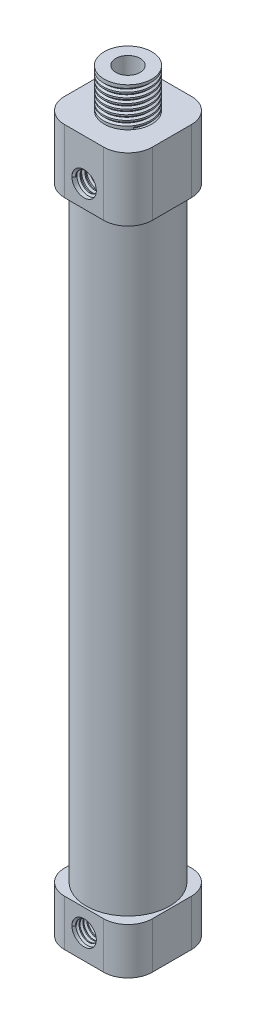
SolidWorks part; units mm, degrees
ref_plane "前视基准面" through (0, 0, 0) normal (0, 0, 1) x (1, 0, 0)
ref_plane "上视基准面" through (0, 0, 0) normal (0, 1, 0) x (1, 0, 0)
ref_plane "右视基准面" through (0, 0, 0) normal (1, 0, 0) x (0, 0, -1)
sketch "草图1" plane through (0, 0, 0) normal (0, 1, 0) x (1, 0, 0)
  circle A0 centre (0, 0) radius 8.54
  dimension "D1" = 17.08
extrude "凸台-拉伸1" add sketch "草图1" along normal blind 124
sketch "草图2" plane through (0, 124, 0) normal (0, 1, 0) x (1, 0, 0)
  line L1 (-9, -9) -> (9, -9)
  line L2 (-9, -9) -> (-9, 9)
  line L3 (-9, 9) -> (9, 9)
  line L4 (9, -9) -> (9, 9)
  line L5 (-9, -9) -> (9, 9) construction
  line L6 (-9, 9) -> (9, -9) construction
  point P0 (0, 0)
  dimension "D1" = 18
extrude "凸台-拉伸2" add sketch "草图2" along normal blind 13
fillet "圆角1" radius 5 4 edges at (9, 130.5, -9) (-9, 130.5, -9) (-9, 130.5, 9) (9, 130.5, 9)
sketch "草图3" plane through (0, 0, 9) normal (0, 0, 1) x (1, 0, 0)
  line L0 (0, 138.947) -> (0, 120.0596) construction
  line L1 (-4, 137) -> (4, 137) construction
  circle A0 centre (0, 128.5) radius 2.5
  dimension "D1" = 5
  dimension "D2" = 6
sketch "草图4" plane through (0, 137, 0) normal (0, 1, 0) x (1, 0, 0)
  circle A0 centre (0, 0) radius 4.875
  dimension "D1" = 9.75
extrude "凸台-拉伸3" add sketch "草图4" along normal blind 8
thread "螺纹线1" pitch 0.7937 method cut profile "螺纹线轮廓1" start angle 0, offset 0, length 7.6, pitch 1, diameter 9.75
ref_plane "基准面1" through (-4.875, 145, 0) normal (0, 0, 1) x (-1, 0, 0)
sketch "螺纹线轮廓1" plane through (-4.875, 145, 0) normal (0, 0, 1) x (-1, 0, 0)
  line L0 (0, 0) -> (0, 0.7937) construction
  line L11 (0, 0) -> (0, 0.6945)
  line L12 (0, 0.6945) -> (-0.4296, 0.4465)
  line L13 (-0.4296, 0.4465) -> (-0.4296, 0.248)
  line L15 (-0.4296, 0.248) -> (0, 0)
  line L17 (-0.4296, 0.3473) -> (0, 0.3473) construction
  point P2 (0, 0)
  dimension "Pitch" = 0.7937
  dimension "Profile_Angle" = 60
  dimension "Profile_Land" = 0.1984
  dimension "Profile_Height" = 0.4296
sketch "草图9" plane through (0, 145, 0) normal (0, 1, 0) x (1, 0, 0)
  circle A0 centre (0, 0) radius 2.5
  dimension "D1" = 5
extrude "切除-拉伸1" cut sketch "草图9" against normal through all
extrude "切除-拉伸2" cut sketch "草图3" against normal up to next contours A0
thread "螺纹线3" pitch 0.7937 method extrude profile "螺纹线轮廓2" start angle 0, offset 0, length 6.1, pitch 1, diameter 5
ref_plane "基准面2" through (-2.5, 128.5, 9) normal (0, -1, 0) x (-1, 0, 0)
sketch "螺纹线轮廓2" plane through (-2.5, 128.5, 9) normal (0, -1, 0) x (-1, 0, 0)
  line L0 (0, 0) -> (0, 0.7937) construction
  line L11 (0, 0) -> (0, 0.6945)
  line L12 (0, 0.6945) -> (-0.4296, 0.4465)
  line L13 (-0.4296, 0.4465) -> (-0.4296, 0.248)
  line L15 (-0.4296, 0.248) -> (0, 0)
  line L17 (-0.4296, 0.3473) -> (0, 0.3473) construction
  point P2 (0, 0)
  dimension "Pitch" = 0.7937
  dimension "Profile_Angle" = 60
  dimension "Profile_Land" = 0.1984
  dimension "Profile_Height" = 0.4296
sketch "草图12" plane through (0, 0, 0) normal (0, -1, 0) x (1, 0, 0)
  line L4 (-4, -9) -> (4, -9)
  line L5 (9, -4) -> (9, 4)
  line L6 (4, 9) -> (-4, 9)
  line L7 (-9, 4) -> (-9, -4)
  line L8 (-4, -9) -> (4, -9)
  line L9 (9, -4) -> (9, 4)
  line L10 (4, 9) -> (-4, 9)
  line L11 (-9, 4) -> (-9, -4)
  arc A6 (4, -9) -> (9, -4) centre (4, -4) ccw
  arc A7 (9, 4) -> (4, 9) centre (4, 4) ccw
  arc A8 (-4, 9) -> (-9, 4) centre (-4, 4) ccw
  arc A9 (-9, -4) -> (-4, -9) centre (-4, -4) ccw
  arc A10 (4, -9) -> (9, -4) centre (4, -4) ccw
  arc A11 (9, 4) -> (4, 9) centre (4, 4) ccw
  arc A12 (-4, 9) -> (-9, 4) centre (-4, 4) ccw
  arc A13 (-9, -4) -> (-4, -9) centre (-4, -4) ccw
  dimension "D2" = 0
extrude "凸台-拉伸4" add sketch "草图12" along normal blind 9.5 contours A12 L11 A13 L8 A10 L9 A11 L10
sketch "草图13" plane through (0, 0, 0) normal (0, 1, 0) x (1, 0, 0)
  circle A0 centre (0, 0) radius 2.5 construction
  circle A1 centre (0, 0) radius 2.5
extrude "切除-拉伸3" cut sketch "草图13" against normal blind 9
sketch "草图14" plane through (0, 0, 9) normal (0, 0, 1) x (1, 0, 0)
  line L0 (0, -10.7455) -> (0, 3.5915) construction
  line L1 (4, 0) -> (-4, 0) construction
  circle A0 centre (0, -4.5) radius 2.5
  dimension "D1" = 5
  dimension "D2" = 2
extrude "切除-拉伸4" cut sketch "草图14" against normal up to next
thread "螺纹线5" pitch 0.7937 method extrude profile "螺纹线轮廓5" start angle 0, offset 0, length 6.1, pitch 0.7937, diameter 5
ref_plane "基准面5" through (-2.5, -4.5, 9) normal (0, -1, 0) x (-1, 0, 0)
sketch "螺纹线轮廓5" plane through (-2.5, -4.5, 9) normal (0, -1, 0) x (-1, 0, 0)
  line L0 (0, 0) -> (0, 0.7937) construction
  line L11 (0, 0) -> (0, 0.6945)
  line L12 (0, 0.6945) -> (-0.4296, 0.4465)
  line L13 (-0.4296, 0.4465) -> (-0.4296, 0.248)
  line L15 (-0.4296, 0.248) -> (0, 0)
  line L17 (-0.4296, 0.3473) -> (0, 0.3473) construction
  point P2 (0, 0)
  dimension "Pitch" = 0.7937
  dimension "Profile_Angle" = 60
  dimension "Profile_Land" = 0.1984
  dimension "Profile_Height" = 0.4296
